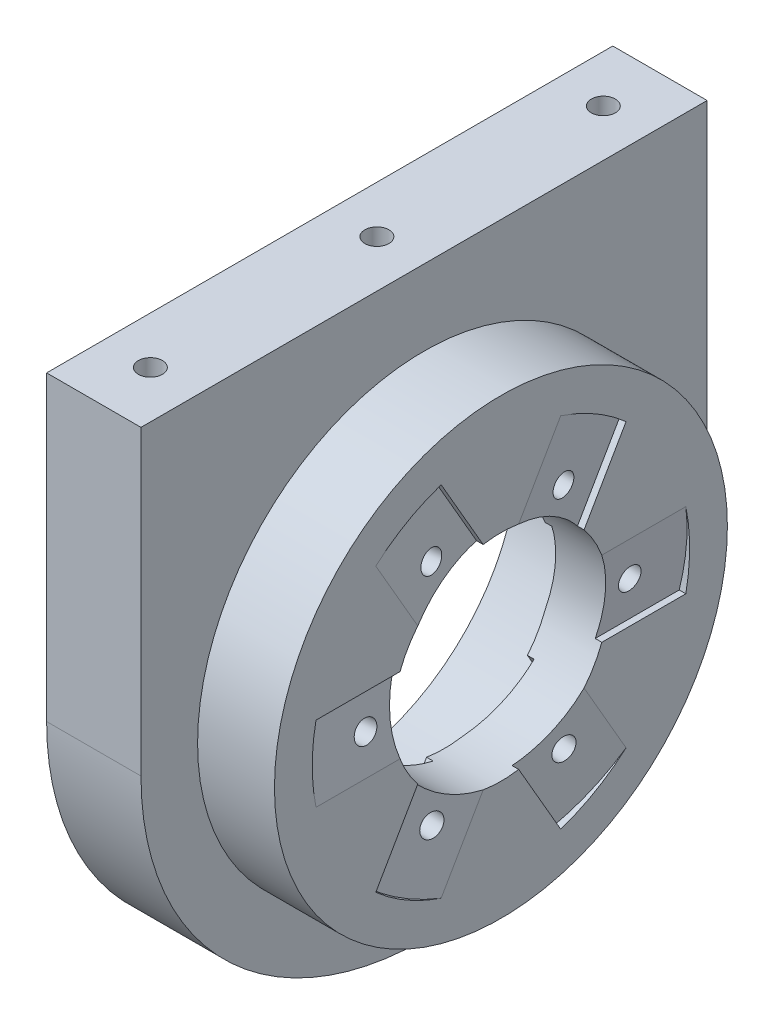
SolidWorks part; units mm, degrees
ref_plane "Front Plane" through (0, 0, 0) normal (0, 0, 1) x (1, 0, 0)
ref_plane "Top Plane" through (0, 0, 0) normal (0, 1, 0) x (1, 0, 0)
ref_plane "Right Plane" through (0, 0, 0) normal (1, 0, 0) x (0, 0, -1)
sketch "Sketch1" plane through (0, 0, 0) normal (0, 0, 1) x (1, 0, 0)
  line L0 (104.775, 1038.225) -> (104.775, 1044.575)
  line L1 (104.775, 1044.575) -> (114.3, 1044.575)
  line L2 (114.3, 1044.575) -> (114.3, 1054.1)
  line L3 (114.3, 1054.1) -> (120.65, 1054.1)
  line L4 (120.65, 1054.1) -> (120.65, 1044.575)
  line L5 (120.65, 1044.575) -> (133.5824, 1044.575)
  line L6 (133.5824, 1044.575) -> (133.5824, 1038.225)
  line L9 (133.5824, 1038.225) -> (104.775, 1038.225)
  line L10 (184.3824, 1006.475) -> (0, 1006.475) construction
revolve "Revolve1" add sketch "Sketch1" angle 360 about L10
sketch "Sketch2" plane through (114.3, 0, 0) normal (-1, 0, 0) x (0, 0, 1)
  circle A0 centre (0, 1006.475) radius 38.1 construction
  circle A1 centre (0, 1006.475) radius 47.625
  circle A2 centre (0, 1006.475) radius 47.625
  circle A3 centre (0, 1006.475) radius 38.1
  dimension "D1" = 0
extrude "Boss-Extrude1" [suppressed] add sketch "Sketch2" along normal blind 20
sketch "Sketch3" plane through (0, 0, 0) normal (0, 1, 0) x (1, 0, 0)
  circle A0 centre (0, 0) radius 114.3
extrude "Cut-Extrude2" [suppressed] cut sketch "Sketch3" along normal through all
sketch "Sketch4" plane through (104.775, 0, 0) normal (-1, 0, 0) x (0, 0, 1)
  circle A0 centre (0, 1006.475) radius 38.1
  circle A1 centre (0, 1006.475) radius 31.75
  dimension "D2" = 76.2
extrude "Boss-Extrude2" [suppressed] add sketch "Sketch4" along normal blind 12.7 and the other way up to body separate body
sketch "Sketch5" plane through (0, 0, 0) normal (0, 1, 0) x (1, 0, 0)
  circle A0 centre (0, 0) radius 104.775
extrude "Cut-Extrude3" [suppressed] cut sketch "Sketch5" along normal through all
sketch "Sketch7" plane through (133.5824, 0, 0) normal (1, 0, 0) x (0, 0, -1)
  circle A0 centre (0, 1006.475) radius 38.1
  circle A1 centre (0, 1006.475) radius 18.1229
  circle A2 centre (0, 1006.475) radius 38.1 construction
  dimension "D1" = 36.2458
extrude "Boss-Extrude3" add sketch "Sketch7" against normal blind 9.525
sketch "Sketch15" plane through (133.5824, 0, 0) normal (1, 0, 0) x (0, 0, -1)
  line L0 (0, 1006.475) -> (22.225, 1006.475) construction
  circle A0 centre (0, 1006.475) radius 22.225 construction
  dimension "D1" = 44.45
sketch "Sketch8" plane through (0, 0, 0) normal (0, 0, 1) x (1, 0, 0)
  line L0 (133.5824, 1000.125) -> (133.5824, 1012.825)
  line L1 (133.5824, 1012.825) -> (124.0574, 1012.825) construction
  line L2 (124.0574, 1012.825) -> (124.0574, 1000.125)
  line L3 (124.0574, 1000.125) -> (133.5824, 1000.125) construction
  line L4 (124.0574, 1024.5979) -> (124.0574, 988.3521) construction
  line L5 (184.3824, 1006.475) -> (0, 1006.475) construction
  line L6 (184.3824, 1006.475) -> (0, 1006.475) construction
  line L7 (133.5824, 988.3521) -> (133.5824, 1024.5979) construction
  line L8 (133.5824, 1000.125) -> (132.4713, 1000.125)
  line L9 (132.4713, 1000.125) -> (133.5824, 1012.825)
  line L10 (124.0574, 1012.825) -> (125.1685, 1012.825)
  line L12 (125.1685, 1012.825) -> (124.0574, 1000.125)
  line L13 (124.0574, 1038.225) -> (124.0574, 974.725) construction
  dimension "D1" = 5
  dimension "D2" = 12.7
extrude "Cut-Extrude4" cut sketch "Sketch8" against normal up to surface (31.1085 mm away) up to face at (104.775, 1006.475, -31.75)
hole_wizard "#10-24 Tapped Hole2" positions "Sketch16" profile "Sketch18" tap size "#10-24" standard "ANSI Inch"
sketch "Sketch16" plane through (44.6301, -3.9046, 0) normal (0.9962, -0.0872, 0) x (0, 0, -1)
  point P0 (22.225, 1014.2875)
sketch "Sketch18" plane through (133.0311, 1006.5232, -22.225) normal (0, 0, 1) x (0.0872, 0.9962, 0)
  line L0 (0, 0) -> (0, 16.1268)
  line L1 (0, 16.1268) -> (1.8986, 14.986)
  line L2 (1.8986, 14.986) -> (1.8986, 0)
  line L5 (1.8986, 0) -> (0, 0)
  line L10 (0, 16.1268) -> (-1.8986, 14.986) construction
  line L11 (0, -6.35) -> (0, 107.95) construction
  dimension "Tap Drill Dia." = 3.7973
  dimension "Tap Drill Depth" = 14.986
  dimension "Drill Angle" = 118
cosmetic thread "Hole Thread7" parameters "D1"=8.3819, "D2"=4.826
pattern_circular "CirPattern1" count 6 over 360 about axis through (0, 1006.475, 0) along (1, 0, 0) of "Cut-Extrude4", "#10-24 Tapped Hole2"
hole_wizard "#10-24 Tapped Hole1" [suppressed] positions "Sketch12" profile "Sketch13" tap size "#10-24" standard "ANSI Inch"
sketch "Sketch12" plane through (123.825, 0, 0) normal (1, 0, 0) x (0, 0, -1)
  circle A0 centre (0, 1006.475) radius 42.8625 construction
  circle A1 centre (0, 1006.475) radius 47.625 construction
  point P4 (42.8625, 1006.475)
  point P35 (21.4313, 969.355)
  point P36 (-21.4313, 969.355)
  point P37 (-42.8625, 1006.475)
  point P38 (-21.4313, 1043.595)
  point P39 (21.4313, 1043.595)
  dimension "D1" = 4.7625
  dimension "D2" = 6
sketch "Sketch13" plane through (123.825, 1006.475, -42.8625) normal (0, 1, 0) x (0, 0, -1)
  line L0 (0, 0) -> (0, 15.875)
  line L1 (0, 15.875) -> (1.8986, 15.875)
  line L2 (1.8986, 15.875) -> (1.8986, 0)
  line L5 (1.8986, 0) -> (0, 0)
  line L11 (0, -6.35) -> (0, 107.95) construction
  dimension "Thru Tap Drill Dia." = 3.7973
  dimension "Thru Tap Drill Depth" = 15.875
cosmetic thread "Hole Thread1" [suppressed] parameters "D2"=4.826
cosmetic thread "Hole Thread2" [suppressed] parameters "D2"=4.826
cosmetic thread "Hole Thread3" [suppressed] parameters "D2"=4.826
cosmetic thread "Hole Thread4" [suppressed] parameters "D2"=4.826
cosmetic thread "Hole Thread5" [suppressed] parameters "D2"=4.826
cosmetic thread "Hole Thread6" [suppressed] parameters "D2"=4.826
sketch "Sketch19" plane through (120.65, 0, 0) normal (-1, 0, 0) x (0, 0, 1)
  line L1 (-47.625, 1006.475) -> (-47.625, 1057.275)
  line L2 (-47.625, 1057.275) -> (47.625, 1057.275)
  line L3 (47.625, 1057.275) -> (47.625, 1006.475)
  line L4 (-101.6, 1057.275) -> (101.6, 1057.275) construction
  arc A0 (-47.625, 1006.475) -> (47.625, 1006.475) centre (0, 1006.475) ccw
  circle A2 centre (0, 1006.475) radius 38.1
  circle A3 centre (0, 1006.475) radius 38.1
  dimension "D1" = 95.25
  dimension "D2" = 0
extrude "Boss-Extrude4" add sketch "Sketch19" along normal up to surface (15.875 mm away) up to face at (104.775, 1006.475, -31.75)
hole_wizard "#10-32 Tapped Hole1" positions "Sketch20" profile "Sketch21" tap size "#10-32" standard "ANSI Inch"
sketch "Sketch20" plane through (0, 1057.275, 0) normal (0, 1, 0) x (1, 0, 0)
  line L0 (112.7125, 38.1) -> (112.7125, -38.1) construction
  line L2 (184.3824, 0) -> (0, 0) construction
  line L3 (104.775, 0) -> (120.65, 0) construction
  line L4 (104.775, -47.625) -> (104.775, 47.625) construction
  line L5 (120.65, -38.1) -> (120.65, 38.1) construction
  point P0 (112.7125, 38.1)
  point P2 (112.7125, 0)
  point P4 (112.7125, -38.1)
  dimension "D1" = 38.1
sketch "Sketch21" plane through (112.7125, 1057.275, -38.1) normal (1, 0, 0) x (0, 0, 1)
  line L0 (0, 0) -> (0, 13.9133)
  line L1 (0, 13.9133) -> (2.0193, 12.7)
  line L2 (2.0193, 12.7) -> (2.0193, 0)
  line L5 (2.0193, 0) -> (0, 0)
  line L10 (0, 13.9133) -> (-2.0193, 12.7) construction
  line L11 (0, -6.35) -> (0, 107.95) construction
  dimension "Tap Drill Dia." = 4.0386
  dimension "Tap Drill Depth" = 12.7
  dimension "Drill Angle" = 118
cosmetic thread "Hole Thread8" parameters "D1"=9.652, "D2"=4.826
cosmetic thread "Hole Thread9" parameters "D1"=9.652, "D2"=4.826
cosmetic thread "Hole Thread10" parameters "D1"=9.652, "D2"=4.826
